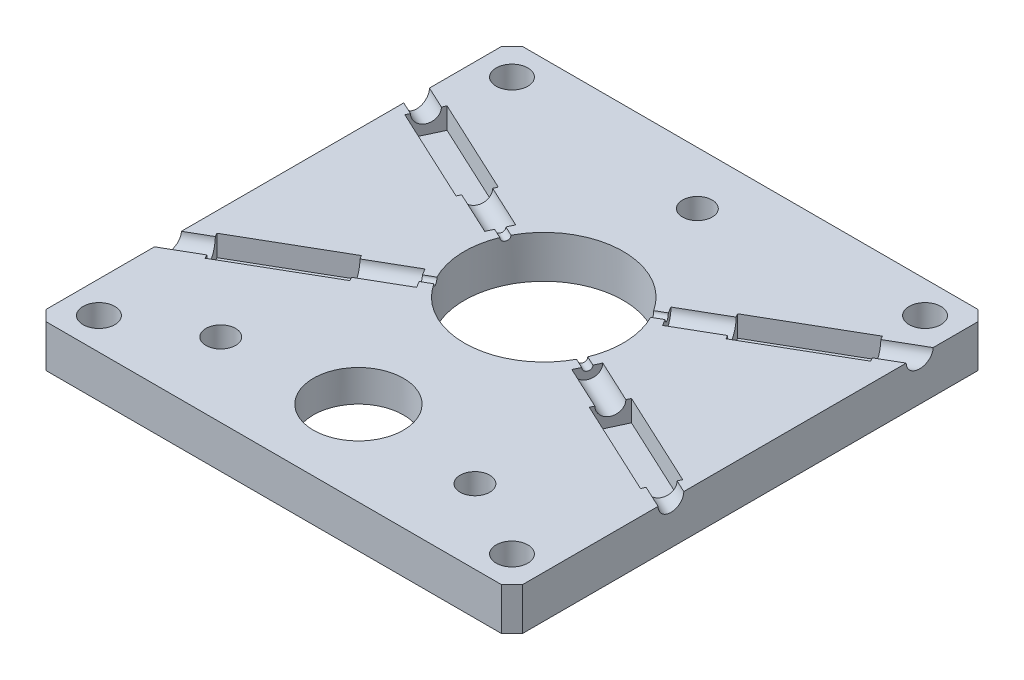
SolidWorks part; units mm, degrees
ref_plane "前视基准面" through (0, 0, 0) normal (0, 0, 1) x (1, 0, 0)
ref_plane "上视基准面" through (0, 0, 0) normal (0, 1, 0) x (1, 0, 0)
ref_plane "右视基准面" through (0, 0, 0) normal (1, 0, 0) x (0, 0, -1)
sketch "草图1" plane through (0, 0, 0) normal (0, 1, 0) x (1, 0, 0)
  line L1 (-22.5, -22.5) -> (22.5, -22.5)
  line L2 (-22.5, -22.5) -> (-22.5, 22.5)
  line L3 (-22.5, 22.5) -> (22.5, 22.5)
  line L4 (22.5, -22.5) -> (22.5, 22.5)
  line L5 (-22.5, -22.5) -> (22.5, 22.5) construction
  line L6 (-22.5, 22.5) -> (22.5, -22.5) construction
  point P0 (0, 0)
  dimension "D1" = 45
  dimension "D2" = 45
extrude "凸台-拉伸1" add sketch "草图1" along normal blind 4
sketch "草图2" plane through (0, 4, 0) normal (0, 1, 0) x (1, 0, 0)
  line L0 (0, 22.5) -> (0, -22.5) construction
  line L1 (22.5, 22.5) -> (-22.5, 22.5) construction
  line L2 (-22.5, -22.5) -> (22.5, -22.5) construction
  circle A0 centre (0, 3) radius 7.5
  dimension "D1" = 3
  dimension "D2" = 15
extrude "切除-拉伸1" cut sketch "草图2" against normal through all
sketch "草图3" plane through (0, 4, 0) normal (0, 1, 0) x (1, 0, 0)
  line L0 (0, 16) -> (0, -10) construction
  line L1 (0, 3) -> (-11.782, 8.494) construction
  line L2 (0, 3) -> (11.2583, 9.5) construction
  line L3 (0, 3) -> (11.782, -2.494) construction
  line L4 (0, 3) -> (-11.2583, -3.5) construction
  circle A0 centre (0, 3) radius 13 construction
  dimension "D1" = 26
  dimension "D2" = 65
  dimension "D3" = 60
  dimension "D4" = 55
ref_plane "基准面1" through (-11.782, 4, -8.494) normal (-0.9063, 0, -0.4226) x (-0.4226, 0, 0.9063)
sketch "草图4" plane through (-11.782, 4, -8.494) normal (-0.9063, 0, -0.4226) x (-0.4226, 0, 0.9063)
  circle A0 centre (0, 0) radius 1.1
  dimension "D1" = 2.2
extrude "切除-拉伸3" cut sketch "草图4" against normal blind 4.5 and the other way through all
sketch "草图10" plane through (-8.8527, 0, -4.1281) normal (-0.9063, 0, -0.4226) x (-0.4226, 0, 0.9063)
  line L0 (-14.5009, 4) -> (9.0631, 4) construction
  circle A0 centre (-2.7189, 4) radius 0.4
  dimension "D1" = 0.8
extrude "切除-拉伸9" cut sketch "草图10" against normal blind 2
sketch "草图6" plane through (0, 0, 0) normal (0, -1, 0) x (1, 0, 0)
  line L0 (0, -22.5) -> (0, 22.5) construction
  line L1 (22.5, -22.5) -> (-22.5, -22.5) construction
  line L2 (-22.5, 22.5) -> (22.5, 22.5) construction
  line L3 (22.5, 0) -> (-22.5, 0) construction
  line L4 (22.5, 22.5) -> (22.5, -22.5) construction
  line L5 (-22.5, -22.5) -> (-22.5, 22.5) construction
  circle A0 centre (19.5, -19.5) radius 3 construction
  circle A1 centre (19.5, -19.5) radius 1.5
  circle A2 centre (-19.5, -19.5) radius 3 construction
  circle A3 centre (-19.5, -19.5) radius 1.5
  circle A4 centre (-19.5, 19.5) radius 1.5
  circle A5 centre (-19.5, 19.5) radius 3 construction
  circle A6 centre (19.5, 19.5) radius 3 construction
  circle A7 centre (19.5, 19.5) radius 1.5
  dimension "D1" = 6
  dimension "D2" = 3
  dimension "D3" = 3
  dimension "D4" = 3
ref_plane "基准面2" through (11.2583, 4, -9.5) normal (0.866, 0, -0.5) x (-0.5, 0, -0.866)
sketch "草图7" plane through (11.2583, 4, -9.5) normal (0.866, 0, -0.5) x (-0.5, 0, -0.866)
  circle A0 centre (0, 0) radius 1.1
  dimension "D1" = 2.2
extrude "切除-拉伸5" cut sketch "草图7" against normal blind 4.5 and the other way through all
sketch "草图11" plane through (8.6603, 0, -5) normal (0.866, 0, -0.5) x (-0.5, 0, -0.866)
  line L0 (3.6981, 4) -> (1.4981, 4) construction
  circle A0 centre (2.5981, 4) radius 0.4
  dimension "D1" = 0.8
extrude "切除-拉伸10" cut sketch "草图11" against normal blind 2
sketch "草图5" plane through (0, 4, 0) normal (0, 1, 0) x (1, 0, 0)
  line L0 (-11.782, 8.494) -> (-12.2469, 7.4971)
  line L1 (-12.2469, 7.4971) -> (-12.4159, 7.1346)
  line L2 (-12.4159, 7.1346) -> (-21.479, 11.3608)
  line L3 (-21.479, 11.3608) -> (-20.2112, 14.0797)
  line L4 (-11.782, 8.494) -> (-20.8451, 12.7202) construction
  line L5 (-11.3171, 9.491) -> (-11.1481, 9.8535)
  line L6 (-11.1481, 9.8535) -> (-20.2112, 14.0797)
  line L7 (0, 3) -> (-11.782, 8.494) construction
  line L8 (-11.3171, 9.491) -> (-11.782, 8.494)
  line L9 (11.2583, 9.5) -> (19.9186, 14.5) construction
  line L10 (0, 3) -> (11.2583, 9.5) construction
  line L11 (12.0083, 8.201) -> (10.5083, 10.799)
  line L12 (15.3833, 2.3553) -> (7.1333, 16.6447) construction
  line L13 (10.5083, 10.799) -> (19.1686, 15.799)
  line L14 (19.1686, 15.799) -> (20.6686, 13.201)
  line L15 (12.0083, 8.201) -> (20.6686, 13.201)
  line L17 (-7.2387, 7.5892) -> (-22.5, 14.7056) construction
  dimension "D1" = 10
  dimension "D2" = 3
  dimension "D3" = 3
  dimension "D4" = 10
extrude "切除-拉伸4" cut sketch "草图5" against normal blind 2
pattern_circular "阵列(圆周)1" count 2 over 360 about axis through (0, 0, -3) along (0, 1, 0) of "切除-拉伸4", "切除-拉伸3", "切除-拉伸5", "切除-拉伸9", "切除-拉伸10"
extrude "切除-拉伸6" cut sketch "草图6" against normal through all
sketch "草图8" plane through (0, 4, 0) normal (0, 1, 0) x (1, 0, 0)
  line L0 (0, -22.5) -> (0, -10) construction
  line L1 (-22.5, -22.5) -> (22.5, -22.5) construction
  circle A0 centre (0, -14.5) radius 4.25
  circle A1 centre (0, -14.5) radius 7.5 construction
  dimension "D1" = 8.5
  dimension "D2" = 8
  dimension "D3" = 15
extrude "切除-拉伸7" cut sketch "草图8" against normal through all
sketch "草图9" plane through (0, 0, 0) normal (0, -1, 0) x (1, 0, 0)
  circle A0 centre (0, 14.5) radius 6
  dimension "D1" = 12
extrude "切除-拉伸8" cut sketch "草图9" against normal blind 1
sketch "草图12" plane through (0, 0, 0) normal (0, 1, 0) x (1, 0, 0)
  line L0 (0, 22.5) -> (0, -22.5) construction
  line L1 (22.5, 22.5) -> (-22.5, 22.5) construction
  line L2 (-22.5, -22.5) -> (22.5, -22.5) construction
  line L3 (-22.5, -15.5) -> (22.5, -15.5) construction
  line L4 (-22.5, -11.2606) -> (-22.5, -22.5) construction
  line L5 (22.5, -22.5) -> (22.5, -8.7056) construction
  circle A0 centre (0, 17.5) radius 1.4
  circle A1 centre (-12, -15.5) radius 1.4
  circle A2 centre (12, -15.5) radius 1.4
  point P12 (0, 17.5)
  point P17 (-12, -15.5)
  dimension "D1" = 2.8
  dimension "D2" = 2.8
  dimension "D3" = 5
  dimension "D6" = 7
  dimension "D7" = 12
extrude "切除-拉伸11" cut sketch "草图12" along normal through all
ref_plane "基准面3" through (0, 10, 0) normal (0, 1, 0) x (1, 0, 0)
chamfer "倒角1" distance 1 angle 45 1 edges at (0, 1, 8.5)
chamfer "倒角2" distance 1 angle 45 4 edges at (22.5, 2, 22.5) (-22.5, 2, 22.5) (22.5, 2, -22.5) (-22.5, 2, -22.5)
chamfer "倒角3" distance 2 angle 45 3 edges at (-12, 0, 16.9) (0, 0, -16.1) (12, 0, 14.1)
